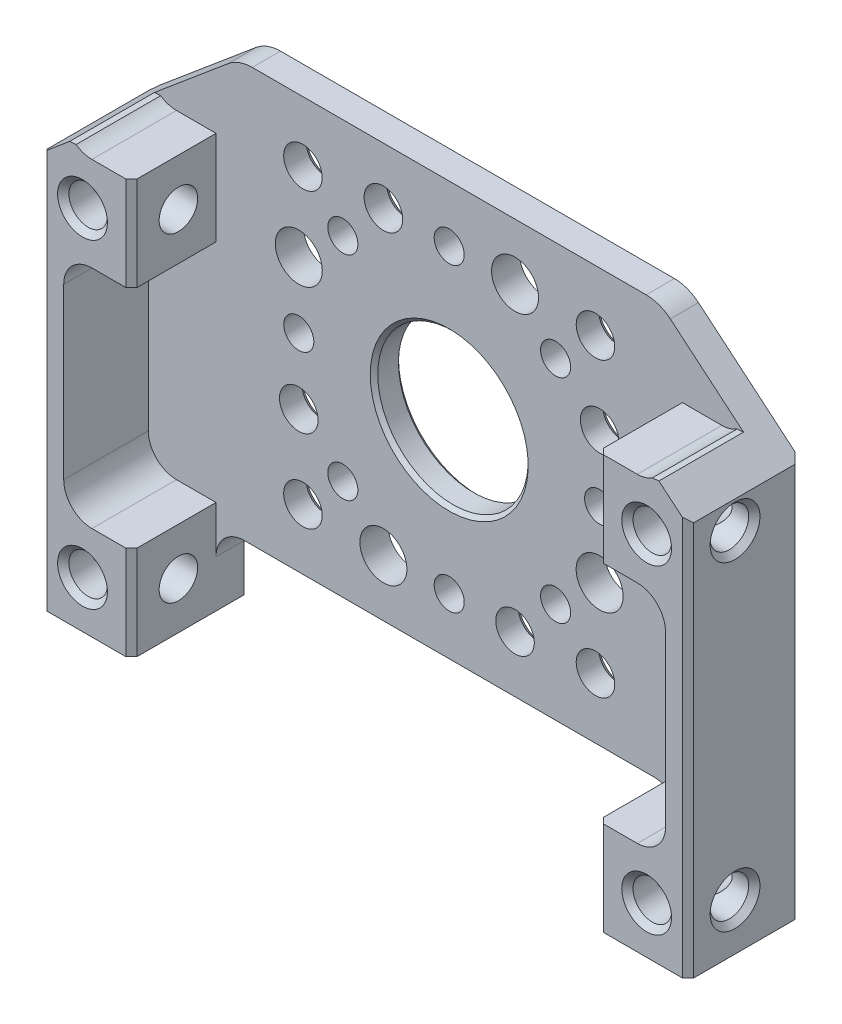
SolidWorks part; units mm, degrees
ref_plane "Front Plane" through (0, 0, 0) normal (0, 0, 1) x (1, 0, 0)
ref_plane "Top Plane" through (0, 0, 0) normal (0, 1, 0) x (1, 0, 0)
ref_plane "Right Plane" through (0, 0, 0) normal (1, 0, 0) x (0, 0, -1)
ref_plane "Plane1" through (0, 0, -15) normal (0, 0, 1) x (1, 0, 0)
sketch "Sketch1" plane through (0, 0, -15) normal (0, 0, 1) x (1, 0, 0)
  line L0 (-17.2, 5.9654) -> (17.2, 5.9654)
  line L1 (17.2, 5.9654) -> (15.5057, 7.3871)
  line L2 (14.5, 7) -> (-14.5, 7)
  line L3 (-15.5057, 7.3871) -> (-17.2, 5.9654)
  arc A0 (15.5057, 7.3871) -> (14.5, 7) centre (14.5, 8.5) cw
  arc A1 (-14.5, 7) -> (-15.5057, 7.3871) centre (-14.5, 8.5) cw
extrude "Boss-Extrude1" add sketch "Sketch1" against normal blind 4.5
sketch "Sketch2" plane through (0, 0, -19.5) normal (0, 0, -1) x (-1, 0, 0)
  line L0 (17.2, 5.9654) -> (-17.2, 5.9654)
  line L1 (-17.2, 5.9654) -> (-11.2, 11)
  line L2 (-11.2, 11) -> (11.2, 11)
  line L3 (11.2, 11) -> (17.2, 5.9654)
extrude "Boss-Extrude2" add sketch "Sketch2" along normal blind 1.5
sketch "Sketch3" plane through (0, 5.9654, 0) normal (0, -1, 0) x (1, 0, 0)
  line L0 (17.2, -15) -> (17.2, -21)
  line L1 (17.2, -21) -> (-17.2, -21)
  line L2 (-17.2, -21) -> (-17.2, -15)
  line L3 (-17.2, -15) -> (17.2, -15)
extrude "Boss-Extrude3" add sketch "Sketch3" along normal blind 16.9654
ref_plane "Plane2" through (12.4, 0, 0) normal (1, 0, 0) x (0, 0, -1)
sketch "Sketch4" plane through (12.4, 0, 0) normal (1, 0, 0) x (0, 0, -1)
  line L0 (15, -11) -> (19.5, -11)
  line L1 (19.5, -11) -> (19.5, 7)
  line L2 (19.5, 7) -> (15, 7)
  line L3 (15, 7) -> (15, -11)
extrude "Cut-Extrude1" cut sketch "Sketch4" against normal blind 24.8
sketch "Sketch5" plane through (0, -11, 0) normal (0, -1, 0) x (1, 0, 0)
  line L0 (17.2, -21) -> (12.4, -21)
  line L1 (12.4, -21) -> (12.4, -15)
  line L2 (12.4, -15) -> (17.2, -15)
  line L3 (17.2, -15) -> (17.2, -21)
extrude "Boss-Extrude4" add sketch "Sketch5" along normal blind 4
sketch "Sketch6" plane through (0, -11, 0) normal (0, -1, 0) x (1, 0, 0)
  line L0 (-17.2, -15) -> (-12.4, -15)
  line L1 (-12.4, -15) -> (-12.4, -21)
  line L2 (-12.4, -21) -> (-17.2, -21)
  line L3 (-17.2, -21) -> (-17.2, -15)
extrude "Boss-Extrude5" add sketch "Sketch6" along normal blind 4
sketch "Sketch7" plane through (-12.4, 0, 0) normal (1, 0, 0) x (0, 0, -1)
  line L0 (19.5, -10) -> (19.5, 2)
  line L1 (19.5, 2) -> (15, 2)
  line L2 (15, 2) -> (15, -10)
  line L3 (15, -10) -> (19.5, -10)
extrude "Cut-Extrude2" cut sketch "Sketch7" against normal blind 3.6
sketch "Sketch8" plane through (0, 0, -15) normal (0, 0, 1) x (1, 0, 0)
  line L0 (16, -10) -> (16, 2)
  line L1 (16, 2) -> (12.4, 2)
  line L2 (12.4, 2) -> (12.4, -10)
  line L3 (12.4, -10) -> (16, -10)
extrude "Cut-Extrude3" cut sketch "Sketch8" against normal blind 4.5
hole_wizard "Ø2.05 (2.05) Diameter Hole1" positions "Sketch10" profile "Sketch9" hole size "Ø2.05" standard "ANSI Metric"
sketch "Sketch10" plane through (-12.4, 0, 0) normal (1, 0, 0) x (0, 0, -1)
  point P0 (17.5, 4.5)
  point P1 (17.5, -12.5)
sketch "Sketch9" plane through (-12.4, 4.5, -17.5) normal (0, 1, 0) x (0, 0, -1)
  line L0 (0, 0) -> (0, 4.8)
  line L1 (0, 4.8) -> (1.025, 4.8)
  line L2 (1.025, 4.8) -> (1.025, 0)
  line L5 (1.025, 0) -> (0, 0)
  line L11 (0, -6.35) -> (0, 107.95) construction
  dimension "Thru Hole Dia." = 2.05
  dimension "Thru Hole Depth" = 4.8
hole_wizard "Ø2.05 (2.05) Diameter Hole2" positions "Sketch12" profile "Sketch11" hole size "Ø2.05" standard "ANSI Metric"
sketch "Sketch12" plane through (12.4, 0, 0) normal (-1, 0, 0) x (0, 0, 1)
  point P0 (-17.5, 4.5)
  point P1 (-17.5, -12.5)
sketch "Sketch11" plane through (12.4, 4.5, -17.5) normal (0, 1, 0) x (0, 0, 1)
  line L0 (0, 0) -> (0, 4.8)
  line L1 (0, 4.8) -> (1.025, 4.8)
  line L2 (1.025, 4.8) -> (1.025, 0)
  line L5 (1.025, 0) -> (0, 0)
  line L11 (0, -6.35) -> (0, 107.95) construction
  dimension "Thru Hole Dia." = 2.05
  dimension "Thru Hole Depth" = 4.8
hole_wizard "Ø2.5 (2.5) Diameter Hole1" positions "Sketch14" profile "Sketch13" hole size "Ø2.5" standard "ANSI Metric"
sketch "Sketch14" plane through (0, 0, -19.5) normal (0, 0, 1) x (1, 0, 0)
  point P0 (3.5, 8)
  point P1 (-8, 3.5)
  point P2 (-3.5, -8)
  point P3 (8, -3.5)
sketch "Sketch13" plane through (3.5, 8, -19.5) normal (1, 0, 0) x (0, -1, 0)
  line L0 (0, 0) -> (0, 1.5001)
  line L1 (0, 1.5001) -> (1.25, 1.5001)
  line L2 (1.25, 1.5001) -> (1.25, 0)
  line L5 (1.25, 0) -> (0, 0)
  line L11 (0, -6.35) -> (0, 107.95) construction
  dimension "Thru Hole Dia." = 2.5
  dimension "Thru Hole Depth" = 1.5001
hole_wizard "Ø2.05 (2.05) Diameter Hole3" positions "Sketch16" profile "Sketch15" hole size "Ø2.05" standard "ANSI Metric"
sketch "Sketch16" plane through (0, 0, -21) normal (0, 0, -1) x (-1, 0, 0)
  point P0 (3.5, 8)
  point P1 (8, -3.5)
  point P2 (-3.5, -8)
  point P3 (-8, 3.5)
  point P4 (7.7782, 7.7782)
  point P5 (7.7782, -7.7782)
  point P6 (-7.7782, -7.7782)
  point P7 (-7.7782, 7.7782)
sketch "Sketch15" plane through (-3.5, 8, -21) normal (1, 0, 0) x (0, 1, 0)
  line L0 (0, 0) -> (0, 6)
  line L1 (0, 6) -> (1.025, 6)
  line L2 (1.025, 6) -> (1.025, 0)
  line L5 (1.025, 0) -> (0, 0)
  line L11 (0, -6.35) -> (0, 107.95) construction
  dimension "Thru Hole Dia." = 2.05
  dimension "Thru Hole Depth" = 6
hole_wizard "Ø1.6 (1.6) Diameter Hole1" positions "Sketch18" profile "Sketch17" hole size "Ø1.6" standard "ANSI Metric"
sketch "Sketch18" plane through (0, 0, -21) normal (0, 0, -1) x (-1, 0, 0)
  point P0 (0, 8)
  point P1 (-5.6569, 5.6569)
  point P2 (-8, 0)
  point P3 (-5.6569, -5.6569)
  point P4 (0, -8)
  point P5 (5.6569, -5.6569)
  point P6 (8, 0)
  point P7 (5.6569, 5.6569)
sketch "Sketch17" plane through (0, 8, -21) normal (1, 0, 0) x (0, 1, 0)
  line L0 (0, 0) -> (0, 6)
  line L1 (0, 6) -> (0.8, 6)
  line L2 (0.8, 6) -> (0.8, 0)
  line L5 (0.8, 0) -> (0, 0)
  line L11 (0, -6.35) -> (0, 107.95) construction
  dimension "Thru Hole Dia." = 1.6
  dimension "Thru Hole Depth" = 6
hole_wizard "Ø8.0 (8) Diameter Hole1" positions "Sketch20" profile "Sketch19" hole size "Ø8.0" standard "ANSI Metric"
sketch "Sketch20" plane through (0, 0, -19.5) normal (0, 0, 1) x (1, 0, 0)
  point P0 (0, 0)
sketch "Sketch19" plane through (0, 0, -19.5) normal (1, 0, 0) x (0, -1, 0)
  line L0 (0, 0) -> (0, 1.5001)
  line L1 (0, 1.5001) -> (4, 1.5001)
  line L2 (4, 1.5001) -> (4, 0)
  line L5 (4, 0) -> (0, 0)
  line L11 (0, -6.35) -> (0, 107.95) construction
  dimension "Thru Hole Dia." = 8
  dimension "Thru Hole Depth" = 1.5001
hole_wizard "Ø2.05 (2.05) Diameter Hole4" positions "Sketch22" profile "Sketch21" hole size "Ø2.05" standard "ANSI Metric"
sketch "Sketch22" plane through (0, 0, -15) normal (0, 0, 1) x (1, 0, 0)
  point P0 (15, 4.5)
  point P1 (-15, 4.5)
  point P2 (15, -12.5)
  point P3 (-15, -12.5)
sketch "Sketch21" plane through (15, 4.5, -15) normal (1, 0, 0) x (0, -1, 0)
  line L0 (0, 0) -> (0, 9.5)
  line L1 (0, 9.5) -> (1.025, 9.5)
  line L2 (1.025, 9.5) -> (1.025, 0)
  line L5 (1.025, 0) -> (0, 0)
  line L10 (0, 9.5) -> (-1.025, 9.5) construction
  line L11 (0, -6.35) -> (0, 107.95) construction
  dimension "Hole Dia." = 2.05
  dimension "Hole Depth" = 9.5
  dimension "Drill Angle" = 180
chamfer "Chamfer1" distance 0.3 angle 45 30 edges at (12.4, -12.5, -15) (17.2, -12.5, -16.475) (17.2, 4.5, -16.475) (6.7532, 7.7782, -21) (6.7532, -7.7782, -21) (-8.8032, -7.7782, -21) (-8.8032, 7.7782, -21) (6.975, 3.5, -21) (2.475, -8, -21) (-9.025, -3.5, -21) (-4.525, 8, -21) (-6.4569, 5.6569, -21) (-8.8, 0, -21) (-6.4569, -5.6569, -21) (-0.8, -8, -21) (4.8569, -5.6569, -21) (7.2, 0, -21) (4.8569, 5.6569, -21) (-0.8, 8, -21) (-13.975, -12.5, -15) (16.025, -12.5, -15) (-13.975, 4.5, -15) (16.025, 4.5, -15) (17.2, -4.5173, -15) (-17.2, -4.5173, -15) (-17.2, -4.5173, -21) (17.2, -4.5173, -21) (-12.4, 4.5, -15) (12.4, 4.5, -15) (-12.4, -12.5, -15)
chamfer "Chamfer2" distance 0.2 angle 45 2 edges at (-4, 0, -21) (4, 0, -19.5)
chamfer "Chamfer3" distance 0.2247 angle 36.835 2 edges
fillet "Fillet1" radius 1.5 6 edges at (16, 2, -17.25) (-16, -10, -17.25) (-16, 2, -17.25) (16, -10, -17.25) (-12.4, -11, -20.25)
fillet "Fillet2" radius 2 2 edges at (11.2, 11, -20.25) (-11.2, 11, -20.25)
